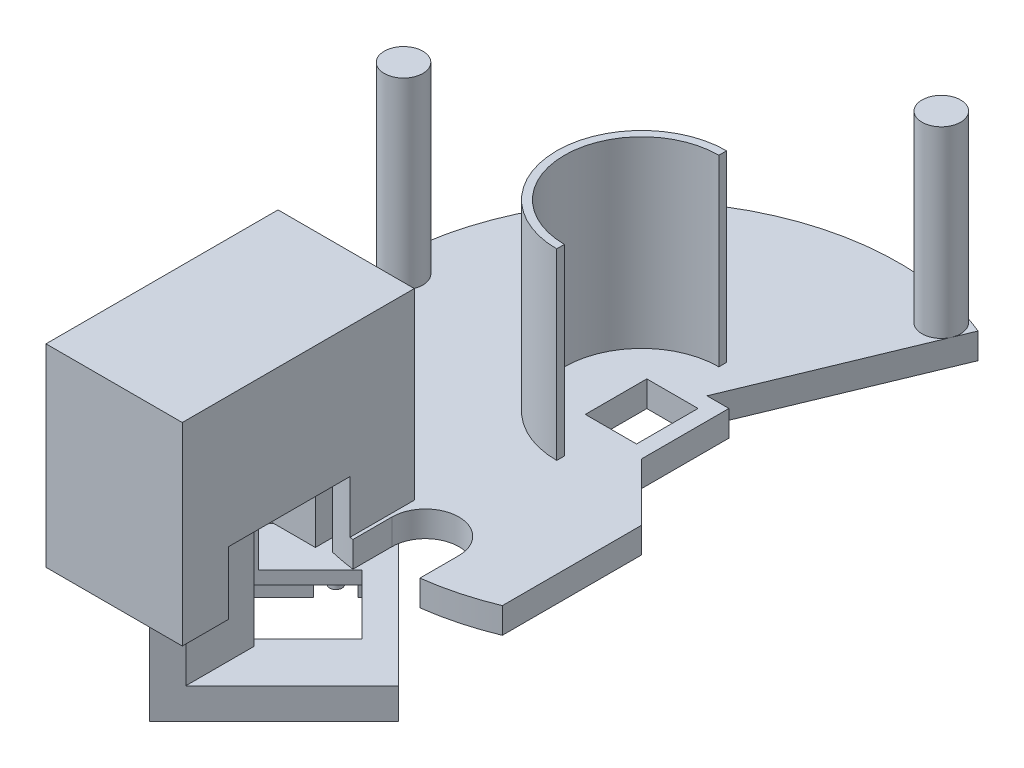
SolidWorks part; units mm, degrees
ref_plane "Front Plane" through (0, 0, 0) normal (0, 0, 1) x (1, 0, 0)
ref_plane "Top Plane" through (0, 0, 0) normal (0, 1, 0) x (1, 0, 0)
ref_plane "Right Plane" through (0, 0, 0) normal (1, 0, 0) x (0, 0, -1)
sketch "Sketch1" plane through (0, 0, 0) normal (0, 1, 0) x (1, 0, 0)
  line L0 (0, -50) -> (0, 0) construction
  line L1 (-4.975, 5.975) -> (4.975, 5.975)
  line L2 (-4.975, 5.975) -> (-4.975, -5.975)
  line L3 (-4.975, -5.975) -> (4.975, -5.975)
  line L4 (4.975, 5.975) -> (4.975, -5.975)
  line L5 (0, -5.975) -> (0, 5.975) construction
  line L6 (-4.975, 0) -> (4.975, 0) construction
  line L7 (7.975, -7.975) -> (35.3553, -35.3553)
  line L8 (0, 0) -> (0, 50) construction
  line L9 (3.7176, 8.975) -> (19.1342, 46.194)
  line L10 (3.7176, 8.975) -> (7.975, 8.975)
  line L11 (7.975, 8.975) -> (7.975, -7.975)
  line L12 (7.975, -7.975) -> (0, 0) construction
  line L13 (0, 0) -> (3.7176, 8.975) construction
  line L14 (6.5, -42) -> (6.5, -49.5757)
  line L15 (-6.5, -42) -> (-6.5, -49.5757)
  arc A0 (6.5, -49.5757) -> (-6.5, -49.5757) centre (0, 0) ccw
  arc A1 (6.5, -42) -> (-6.5, -42) centre (0, -42) ccw
  dimension "D1" = 100
  dimension "D5" = 13
  dimension "D2" = 11.95
  dimension "D3" = 9.95
  dimension "D4" = 45
  dimension "D6" = 42
  dimension "D7" = 22.5
  dimension "D8" = 3
  dimension "D9" = 3
  dimension "D10" = 38.7216
  dimension "D11" = 40.2855
  dimension "D12" = 0
extrude "Boss-Extrude2" add sketch "Sketch1" along normal blind 5 contours L9 A0 L7 L11 L10 A1 L1 L4 L3 L2 region at (-12.9882, 0, 1.1703)
sketch "Sketch4" plane through (0, 5, 0) normal (0, 1, 0) x (1, 0, 0)
  line L0 (0, 16.5) -> (0, 15)
  line L1 (0, -15) -> (0, -16.5)
  arc A0 (0, 15) -> (0, -15) centre (0, 0) ccw
  arc A1 (0, 16.5) -> (0, -16.5) centre (0, 0) ccw
  dimension "D1" = 30
  dimension "D2" = 33
extrude "Boss-Extrude6" add sketch "Sketch4" along normal offset from surface (35.6 mm away) 40.6 up to face at (2.3017, 0, 15.9559)
sketch "Sketch8" plane through (0, 5, 0) normal (0, 1, 0) x (1, 0, 0)
  line L0 (7.975, -7.975) -> (35.3553, -35.3553) construction
  line L1 (3.7176, 8.975) -> (19.1342, 46.194) construction
  circle A0 centre (14.1763, 44.0238) radius 3.75
  circle A1 centre (29.9444, -35.2477) radius 3.75
  circle A2 centre (-46.25, 0) radius 3.75
  arc A3 (19.1342, 46.194) -> (-6.5, -49.5757) centre (0, 0) ccw construction
  arc A4 (6.5, -49.5757) -> (35.3553, -35.3553) centre (0, 0) ccw construction
  dimension "D1" = 7.5
  dimension "D2" = 7.5
  dimension "D3" = 7.5
extrude "Boss-Extrude8" add sketch "Sketch8" along normal up to surface (35.6 mm away) up to face at (-7.875, 40.6, 0)
ref_plane "Plane1" through (0, 3, 0) normal (0, -1, 0) x (-1, 0, 0)
sketch "Sketch9" plane through (0, 3, 0) normal (0, -1, 0) x (-1, 0, 0)
  line L0 (-6.5, -49.5757) -> (6.5, -49.5757) construction
  line L1 (0, -49.5757) -> (0, -56.4663) construction
  line L2 (6.5, -49.5757) -> (11.4, -49.5757) construction
  line L3 (13.8, -49.5757) -> (30.62, -49.5757) construction
  line L4 (7.15, -49.5757) -> (11.4, -49.5757) construction
  line L5 (7.15, -49.5757) -> (7.15, -73.0757) construction
  line L6 (7.15, -73.0757) -> (11.4, -73.0757) construction
  line L7 (30.62, -49.5757) -> (30.62, -73.0757) construction
  line L9 (11.4, -73.0757) -> (11.4, -79.0757)
  line L10 (11.4, -79.0757) -> (13.8, -79.0757)
  line L11 (13.8, -73.0757) -> (13.8, -79.0757)
  line L13 (11.4, -49.5757) -> (11.4, -43.5757)
  line L14 (11.4, -43.5757) -> (13.8, -43.5757)
  line L15 (13.8, -49.5757) -> (13.8, -43.5757)
  line L16 (7.15, -49.5757) -> (11.4, -49.5757)
  line L17 (7.15, -49.5757) -> (7.15, -73.0757)
  line L18 (7.15, -73.0757) -> (11.4, -73.0757)
  line L19 (30.62, -49.5757) -> (30.62, -73.0757)
  line L20 (13.8, -49.5757) -> (30.62, -49.5757) construction
  line L21 (13.8, -49.5757) -> (30.62, -49.5757)
  line L22 (13.8, -73.0757) -> (30.62, -73.0757) construction
  line L23 (13.8, -73.0757) -> (30.62, -73.0757)
  line L25 (7.15, -37.0094) -> (33.62, -37.0094)
  line L26 (7.15, -37.0094) -> (7.15, -82.0757)
  line L27 (7.15, -82.0757) -> (33.62, -82.0757)
  line L28 (33.62, -37.0094) -> (33.62, -82.0757)
  arc A0 (6.5, -49.5757) -> (-19.1342, 46.194) centre (0, 0) ccw construction
  arc A1 (6.5, -49.5757) -> (-19.1342, 46.194) centre (0, 0) ccw
  dimension "D1" = 7.15
  dimension "D2" = 24.12
  dimension "D3" = 23.5
  dimension "D4" = 6.65
  dimension "D5" = 2.4
  dimension "D6" = 6
  dimension "D7" = 6
  dimension "D8" = 3
  dimension "D9" = 3
extrude "Boss-Extrude9" add sketch "Sketch9" against normal blind 12.22 contours A1 L15 L21 L19 L23 L11 L10 L9 L18 L26 L27 L28 | L26 A1 L13 L14 L15 L25 region at (-10.8773, 3, 76.0757) region at (-17.2175, 3, 41.5129)
extrude "Cut-Extrude1" cut sketch "Sketch9<3>" against normal through all both and the other way through all contours A1 L13 L16 L17 L18 L9 L10 L11 L23 L19 L21 L15 | L13 A1 L15 L14 region at (-18.6947, 3, 61.6368) region at (-12.574, 3, 45.9818)
sketch "Sketch9<3>" plane through (0, 3, 0) normal (0, -1, 0) x (-1, 0, 0) same geometry as "Sketch9"
sketch "Sketch10" plane through (0, 15.22, 0) normal (0, 1, 0) x (1, 0, 0)
  line L1 (-33.62, -82.0757) -> (-7.15, -82.0757)
  line L2 (-33.62, -82.0757) -> (-33.62, -37.0094)
  line L3 (-33.62, -37.0094) -> (-7.15, -37.0094)
  line L4 (-7.15, -82.0757) -> (-7.15, -37.0094)
extrude "Boss-Extrude10" add sketch "Sketch10" along normal up to surface (25.38 mm away) up to face at (-7.875, 40.6, 0)
sketch "Sketch11" plane through (0, 3, 0) normal (0, -1, 0) x (1, 0, 0)
  line L1 (-30.62, 49.5757) -> (-26.9153, 49.5757)
  line L2 (-30.62, 49.5757) -> (-30.62, 44.724)
  line L3 (-30.62, 44.724) -> (-26.9153, 44.724)
  line L4 (-26.9153, 49.5757) -> (-26.9153, 44.724)
  dimension "D1" = 3.7047
  dimension "5" = 4.8517
extrude "Cut-Extrude2" cut sketch "Sketch11" against normal up to surface (12.22 mm away) and the other way through all up to face at (-14.6957, 15.22, 61.2477)
ref_plane "Plane2" through (0, -30, 0) normal (0, -1, 0) x (-1, 0, 0)
sketch "Sketch13" plane through (0, 0, 0) normal (0, -1, 0) x (1, 0, 0)
  line L0 (0, 0) -> (0, 42) construction
  line L1 (0, 0) -> (-35.3553, 35.3553) construction
  arc A0 (-13.8, 48.0579) -> (-33.62, 37.0094) centre (0, 0) ccw construction
  circle A1 centre (-29.6985, 29.6985) radius 6.5 construction
  point P10 (0, 0)
  point P11 (0, 0)
  point P12 (0, 0)
  dimension "D2" = 13
  dimension "D1" = 45
  dimension "D3" = 42
sketch "Sketch14" plane through (0, -30, 0) normal (0, -1, 0) x (-1, 0, 0)
  line L0 (26.4458, -40.8708) -> (40.8708, -26.4458)
  line L1 (40.8708, -26.4458) -> (39.0676, -24.6427)
  line L2 (32.9512, -18.5262) -> (18.5262, -32.9512)
  line L3 (24.6427, -39.0676) -> (26.4458, -40.8708)
  line L4 (0, 0) -> (35.3553, -35.3553) construction
  line L5 (35.4968, -23.9002) -> (29.6985, -29.6985) construction
  line L6 (27.86, -39.4566) -> (21.3546, -32.9512)
  line L7 (21.3546, -32.9512) -> (32.9512, -21.3546)
  line L8 (32.9512, -21.3546) -> (39.4566, -27.86)
  line L9 (22.486, -41.2243) -> (24.6427, -39.0676)
  line L10 (18.1726, -36.911) -> (20.3293, -34.7543)
  line L11 (20.3293, -34.7543) -> (18.5262, -32.9512)
  line L12 (25.7387, -25.7387) -> (31.8552, -31.8552) construction
  line L13 (36.911, -18.1726) -> (34.7543, -20.3293)
  line L14 (41.2243, -22.486) -> (39.0676, -24.6427)
  line L16 (34.7543, -20.3293) -> (32.9512, -18.5262)
  circle A0 centre (20.3293, -39.0676) radius 1.2
  arc A1 (18.1726, -36.911) -> (22.486, -41.2243) centre (20.3293, -39.0676) ccw
  circle A2 centre (39.0676, -20.3293) radius 1.2
  arc A3 (36.911, -18.1726) -> (41.2243, -22.486) centre (39.0676, -20.3293) cw
  point P4 (33.6583, -33.6583)
  point P7 (32.9512, -18.5262)
  point P8 (0, 0)
  point P9 (39.0677, -24.6427)
  point P30 (39.0676, -20.3293)
  point P31 (31.8552, -31.8552)
  point P33 (32.9512, -21.3546)
  dimension "D8" = 6.1
  dimension "D9" = 2.4
  dimension "D1" = 11.2
  dimension "D2" = 20.4
  dimension "D3" = 90
  dimension "D4" = 90
  dimension "D5" = 2
  dimension "D6" = 2
  dimension "D7" = 2
  dimension "D10" = 90
  dimension "D11" = 90
extrude "Boss-Extrude11" add sketch "Sketch14" against normal blind 2.5 separate body contours A3 L13 L16 L2 L11 L10 A1 L9 L3 L0 L6 L7 L8 L1 L14 A0 A2 region at (-25.7926, -30, 39.7208)
sketch "Sketch15" plane through (0, -27.5, 0) normal (0, 1, 0) x (1, 0, 0)
  line L0 (-40.8708, -26.4458) -> (-47.3054, -20.0111)
  line L1 (-47.3054, -20.0111) -> (-37.2645, -9.9702)
  line L2 (-37.2645, -9.9702) -> (-9.9702, -37.2645)
  line L3 (-9.9702, -37.2645) -> (-20.0111, -47.3054)
  line L4 (-20.0111, -47.3054) -> (-26.4458, -40.8708)
  line L5 (-39.4566, -27.86) -> (-40.8708, -26.4458) construction
  line L7 (-32.9512, -18.5262) -> (-18.5262, -32.9512) construction
  line L22 (-41.2243, -22.486) -> (-39.0676, -24.6427)
  line L23 (-39.0676, -24.6427) -> (-40.8708, -26.4458)
  line L24 (-40.8708, -26.4458) -> (-39.4566, -27.86)
  line L25 (-39.4566, -27.86) -> (-32.9512, -21.3546)
  line L26 (-32.9512, -21.3546) -> (-21.3546, -32.9512)
  line L27 (-21.3546, -32.9512) -> (-27.86, -39.4566)
  line L28 (-27.86, -39.4566) -> (-26.4458, -40.8708)
  line L29 (-26.4458, -40.8708) -> (-24.6427, -39.0676)
  line L30 (-24.6427, -39.0676) -> (-22.486, -41.2243)
  line L31 (-18.1726, -36.911) -> (-20.3293, -34.7543)
  line L32 (-20.3293, -34.7543) -> (-18.5262, -32.9512)
  line L33 (-18.5262, -32.9512) -> (-32.9512, -18.5262)
  line L34 (-32.9512, -18.5262) -> (-34.7543, -20.3293)
  line L35 (-34.7543, -20.3293) -> (-36.911, -18.1726)
  line L36 (-41.2243, -22.486) -> (-39.0676, -24.6427)
  line L37 (-39.0676, -24.6427) -> (-40.8708, -26.4458)
  line L43 (-26.4458, -40.8708) -> (-24.6427, -39.0676)
  line L44 (-24.6427, -39.0676) -> (-22.486, -41.2243)
  line L45 (-18.1726, -36.911) -> (-20.3293, -34.7543)
  line L46 (-20.3293, -34.7543) -> (-18.5262, -32.9512)
  line L47 (-18.5262, -32.9512) -> (-32.9512, -18.5262)
  line L48 (-32.9512, -18.5262) -> (-34.7543, -20.3293)
  line L49 (-34.7543, -20.3293) -> (-36.911, -18.1726)
  arc A1 (-36.911, -18.1726) -> (-41.2243, -22.486) centre (-39.0676, -20.3293) ccw construction
  arc A4 (-36.911, -18.1726) -> (-41.2243, -22.486) centre (-39.0676, -20.3293) ccw
  arc A5 (-22.486, -41.2243) -> (-18.1726, -36.911) centre (-20.3293, -39.0676) ccw
  arc A6 (-36.911, -18.1726) -> (-41.2243, -22.486) centre (-39.0676, -20.3293) ccw
  arc A7 (-22.486, -41.2243) -> (-18.1726, -36.911) centre (-20.3293, -39.0676) ccw
  point P10 (-3.9648, -31.9221)
  point P16 (-41.2243, -18.1726)
  point P17 (-18.1726, -41.2243)
  dimension "D1" = 90
  dimension "D2" = 3
  dimension "D3" = 90
  dimension "D4" = 90
  dimension "D5" = 3
  dimension "D7" = 3
  dimension "D6" = 0
extrude "Boss-Extrude12" add sketch "Sketch15" against normal blind 6
sketch "Sketch17" plane through (0, -27.5, 0) normal (0, 1, 0) x (1, 0, 0)
  circle A0 centre (-39.0676, -20.3293) radius 1.2
  circle A1 centre (-20.3293, -39.0676) radius 1.2
  circle A2 centre (-39.0676, -20.3293) radius 1.2 construction
extrude "Boss-Extrude13" add sketch "Sketch17" against normal up to surface (6 mm away) up to face at (-29.4333, -33.5, 29.4333)
sketch "Sketch18" plane through (0, -33.5, 0) normal (0, -1, 0) x (1, 0, 0)
  line L1 (19.1342, -46.194) -> (39.1342, -46.194)
  line L2 (19.1342, -46.194) -> (19.1342, 53.806)
  line L3 (19.1342, 53.806) -> (39.1342, 53.806)
  line L4 (39.1342, -46.194) -> (39.1342, 53.806)
  dimension "D1" = 20
  dimension "D2" = 100
extrude "Cut-Extrude3" cut sketch "Sketch18" against normal through all both and the other way through all
sketch "Sketch19" plane through (-33.6583, 0, 33.6583) normal (-0.7071, 0, 0.7071) x (0.7071, 0, 0.7071)
  line L0 (8.2, -30) -> (10.2, -30) construction
  line L1 (10.2, -30) -> (10.2, -33.5) construction
  line L2 (10.2, -33.5) -> (19.3, -33.5) construction
  line L3 (19.3, -33.5) -> (19.3, -27.5) construction
  line L4 (19.3, -27.5) -> (8.2, -27.5) construction
  line L5 (8.2, -27.5) -> (8.2, -30) construction
  line L6 (-10.2, -30) -> (-8.2, -30) construction
  line L7 (-8.2, -30) -> (-8.2, -27.5) construction
  line L8 (-8.2, -27.5) -> (-19.3, -27.5) construction
  line L9 (-19.3, -27.5) -> (-19.3, -33.5) construction
  line L10 (-19.3, -33.5) -> (-10.2, -33.5) construction
  line L11 (-10.2, -33.5) -> (-10.2, -30) construction
  line L12 (8.2, -30) -> (10.2, -30)
  line L13 (10.2, -30) -> (10.2, -33.5)
  line L14 (10.2, -33.5) -> (19.3, -33.5)
  line L15 (19.3, -33.5) -> (19.3, -27.5)
  line L16 (19.3, -27.5) -> (8.2, -27.5)
  line L17 (8.2, -27.5) -> (8.2, -30)
  line L18 (-10.2, -30) -> (-8.2, -30)
  line L19 (-8.2, -30) -> (-8.2, -27.5)
  line L20 (-8.2, -27.5) -> (-19.3, -27.5)
  line L21 (-19.3, -27.5) -> (-19.3, -33.5)
  line L22 (-19.3, -33.5) -> (-10.2, -33.5)
  line L23 (-10.2, -33.5) -> (-10.2, -30)
extrude "Boss-Extrude14" add sketch "Sketch19" along normal blind 20
sketch "Sketch20" plane through (0, 5, 0) normal (0, 1, 0) x (1, 0, 0)
  line L0 (-61.4476, -34.1533) -> (-44.8583, -17.564)
  line L1 (-37.2645, -9.9702) -> (-61.4476, -34.1533) construction
  line L2 (-44.8583, -17.564) -> (-37.0094, -25.4128)
  line L3 (-32.9512, -21.3546) -> (-53.5987, -42.0021) construction
  line L4 (-37.0094, -25.4128) -> (-53.5987, -42.0021)
  line L5 (-53.5987, -42.0021) -> (-61.4476, -34.1533) construction
  line L6 (-53.5987, -42.0021) -> (-61.4476, -34.1533)
  line L7 (-42.0021, -53.5987) -> (-34.1533, -61.4476)
  line L8 (-34.1533, -61.4476) -> (-17.564, -44.8583)
  line L9 (-17.564, -44.8583) -> (-25.4128, -37.0094)
  line L10 (-42.0021, -53.5987) -> (-21.3546, -32.9512) construction
  line L11 (-25.4128, -37.0094) -> (-42.0021, -53.5987)
  line L12 (-33.62, -37.0094) -> (-7.15, -37.0094) construction
  point P16 (-17.8653, -45.1597)
  point P20 (-28.4832, -40.0797)
  point P21 (0, 0)
extrude "Boss-Extrude15" add sketch "Sketch20" against normal blind 5
sketch "Sketch21" plane through (0, 15.22, 0) normal (0, -1, 0) x (1, 0, 0)
  line L13 (-7.15, 49.4861) -> (-7.15, 73.0757)
  line L14 (-7.15, 73.0757) -> (-11.4, 73.0757)
  line L15 (-11.4, 73.0757) -> (-11.4, 79.0757)
  line L16 (-11.4, 79.0757) -> (-13.8, 79.0757)
  line L17 (-13.8, 79.0757) -> (-13.8, 73.0757)
  line L18 (-13.8, 73.0757) -> (-30.62, 73.0757)
  line L19 (-30.62, 73.0757) -> (-30.62, 44.724)
  line L20 (-30.62, 44.724) -> (-26.9153, 44.724)
  line L21 (-26.9153, 44.724) -> (-26.9153, 49.5757)
  line L22 (-26.9153, 49.5757) -> (-13.8, 49.5757)
  line L23 (-13.8, 49.5757) -> (-13.8, 43.5757)
  line L24 (-13.8, 43.5757) -> (-11.4, 43.5757)
  line L25 (-11.4, 43.5757) -> (-11.4, 48.6831)
  line L26 (-7.15, 49.4861) -> (-7.15, 73.0757)
  line L27 (-7.15, 73.0757) -> (-11.4, 73.0757)
  line L28 (-11.4, 73.0757) -> (-11.4, 79.0757)
  line L29 (-11.4, 79.0757) -> (-13.8, 79.0757)
  line L30 (-13.8, 79.0757) -> (-13.8, 73.0757)
  line L31 (-13.8, 73.0757) -> (-30.62, 73.0757)
  line L32 (-30.62, 73.0757) -> (-30.62, 44.724)
  line L33 (-30.62, 44.724) -> (-26.9153, 44.724)
  line L34 (-26.9153, 44.724) -> (-26.9153, 49.5757)
  line L35 (-26.9153, 49.5757) -> (-13.8, 49.5757)
  line L36 (-13.8, 49.5757) -> (-13.8, 43.5757)
  line L37 (-13.8, 43.5757) -> (-11.4, 43.5757)
  line L38 (-11.4, 43.5757) -> (-11.4, 48.6831)
  arc A1 (-7.15, 49.4861) -> (-11.4, 48.6831) centre (0, 0) ccw
  arc A2 (-7.15, 49.4861) -> (-11.4, 48.6831) centre (0, 0) ccw
  dimension "D1" = 0
extrude "Cut-Extrude4" cut sketch "Sketch21" along normal blind 30
sketch "Sketch22" plane through (0, 3, 0) normal (0, -1, 0) x (1, 0, 0)
  line L2 (-29.0784, 40.6749) -> (-33.62, 45.2166)
  line L3 (-33.62, 45.2166) -> (-33.62, 37.0094)
  line L4 (-29.0784, 40.6749) -> (-33.62, 45.2166)
  line L5 (-33.62, 45.2166) -> (-33.62, 37.0094)
  arc A1 (-29.0784, 40.6749) -> (-33.62, 37.0094) centre (0, 0) ccw
  arc A2 (-29.0784, 40.6749) -> (-33.62, 37.0094) centre (0, 0) ccw
  dimension "D1" = 0
extrude "Boss-Extrude16" add sketch "Sketch22" along normal up to surface (3 mm away) up to face at (0, 0, 0)
sketch "Sketch23" plane through (0, 3, 0) normal (0, -1, 0) x (1, 0, 0)
  line L3 (-22.2814, 49.5757) -> (-18.9681, 46.2624)
  line L4 (-13.8, 48.0579) -> (-13.8, 49.5757)
  line L5 (-13.8, 49.5757) -> (-22.2814, 49.5757)
  line L6 (-22.2814, 49.5757) -> (-18.9681, 46.2624)
  line L7 (-13.8, 48.0579) -> (-13.8, 49.5757)
  line L8 (-13.8, 49.5757) -> (-22.2814, 49.5757)
  arc A1 (-13.8, 48.0579) -> (-18.9681, 46.2624) centre (0, 0) ccw
  arc A2 (-13.8, 48.0579) -> (-18.9681, 46.2624) centre (0, 0) ccw
  dimension "D1" = 0
extrude "Boss-Extrude17" add sketch "Sketch23" along normal up to surface (3 mm away) up to face at (-17.7462, 0, 34.3886)
sketch "Sketch24" plane through (0, 0, 0) normal (0, -1, 0) x (1, 0, 0)
  line L0 (-61.4476, 34.1533) -> (-53.5987, 42.0021)
  line L1 (-61.4476, 34.1533) -> (-50.841, 23.5467)
  line L2 (-53.5987, 42.0021) -> (-42.9921, 31.3955)
  line L3 (-50.841, 23.5467) -> (-42.9921, 31.3955)
  line L4 (-53.5987, 42.0021) -> (-40.6749, 29.0784) construction
  line L5 (-34.1533, 61.4476) -> (-30.62, 57.9143)
  line L10 (-30.62, 44.724) -> (-30.62, 57.9143)
  line L12 (-33.62, 45.2166) -> (-30.62, 44.724)
  line L13 (-33.62, 45.2166) -> (-42.0021, 53.5987)
  line L16 (-42.0021, 53.5987) -> (-34.1533, 61.4476)
  dimension "D1" = 15
extrude "Boss-Extrude18" add sketch "Sketch24" along normal up to surface (27.5 mm away) up to face at (-36.5928, -27.5, 36.5928)
